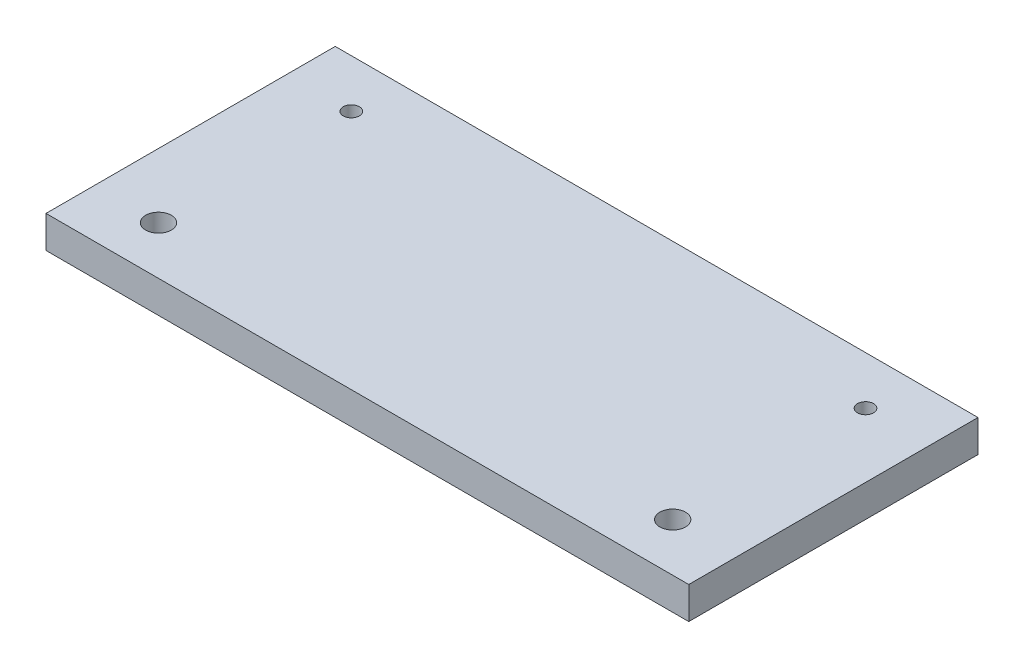
SolidWorks part; units mm, degrees
ref_plane "Front Plane" through (0, 0, 0) normal (0, 0, 1) x (1, 0, 0)
ref_plane "Top Plane" through (0, 0, 0) normal (0, 1, 0) x (1, 0, 0)
ref_plane "Right Plane" through (0, 0, 0) normal (1, 0, 0) x (0, 0, -1)
sketch "Sketch1" plane through (0, 0, 0) normal (0, 1, 0) x (1, 0, 0)
  line L1 (-100, -45) -> (100, -45)
  line L2 (-100, -45) -> (-100, 45)
  line L3 (-100, 45) -> (100, 45)
  line L4 (100, -45) -> (100, 45)
  line L5 (-100, -45) -> (100, 45) construction
  line L6 (-100, 45) -> (100, -45) construction
  point P0 (0, 0)
  dimension "D1" = 200
  dimension "D2" = 90
extrude "Boss-Extrude1" add sketch "Sketch1" along normal blind 10
sketch "Sketch2" plane through (0, 10, 0) normal (0, 1, 0) x (1, 0, 0)
  line L1 (0, 0) -> (0, 1.6072)
  line L4 (-100, -45) -> (100, -45) construction
  circle A0 centre (-80, -30) radius 4
  circle A2 centre (80, -30) radius 4
  dimension "D1" = 8
  dimension "D2" = 80
  dimension "D3" = 15
extrude "Cut-Extrude1" cut sketch "Sketch2" against normal blind 10 contours A0 | A2
sketch "Sketch4" plane through (0, 10, 0) normal (0, 1, 0) x (1, 0, 0)
  line L0 (100, 45) -> (-100, 45) construction
  line L2 (0, 0) -> (0, 10)
  circle A0 centre (-80, 30) radius 2.5
  circle A2 centre (80, 30) radius 2.5
  dimension "D1" = 5
  dimension "D2" = 15
extrude "Cut-Extrude2" cut sketch "Sketch4" against normal blind 10 contours A0 | A2
